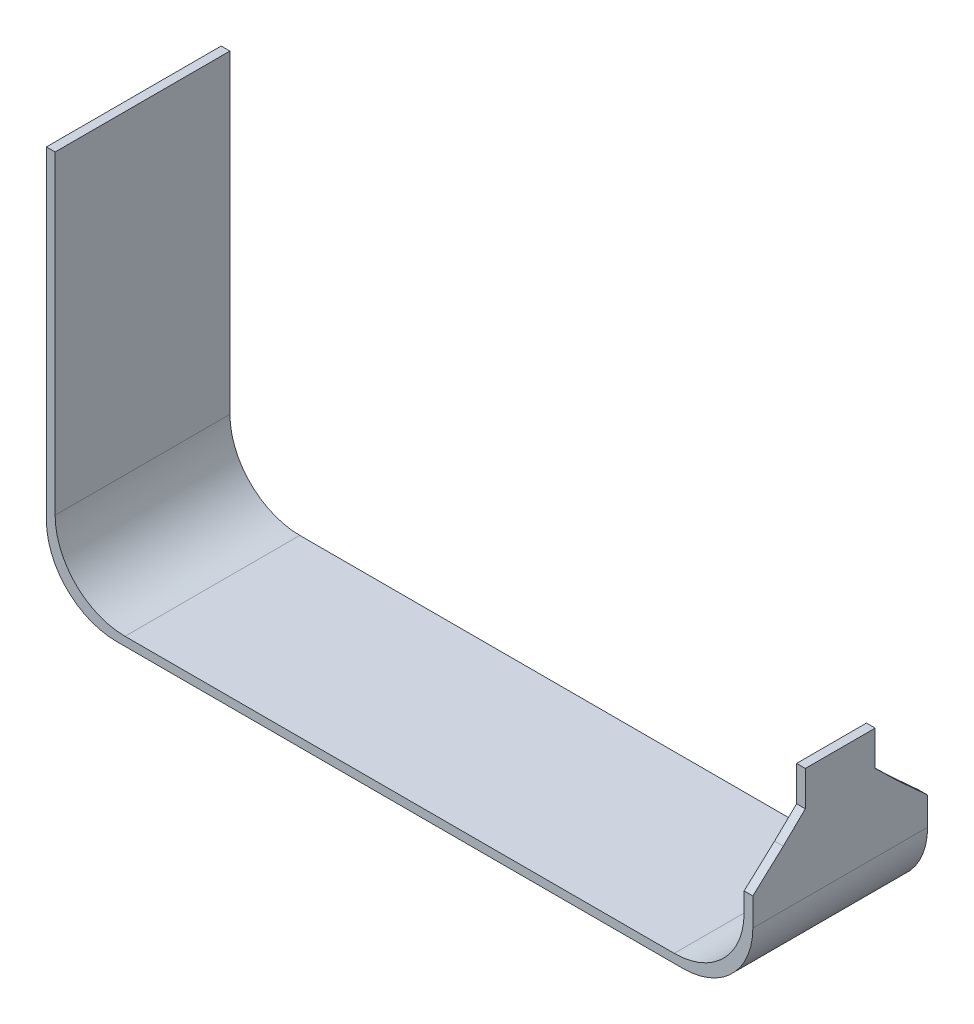
SolidWorks part; units mm, degrees
material "Copper"
ref_plane "Front Plane" through (0, 0, 0) normal (0, 0, 1) x (1, 0, 0)
ref_plane "Top Plane" through (0, 0, 0) normal (0, 1, 0) x (1, 0, 0)
ref_plane "Right Plane" through (0, 0, 0) normal (1, 0, 0) x (0, 0, -1)
sketch "Sketch1" plane through (0, 0, 0) normal (0, 1, 0) x (1, 0, 0)
  line L1 (-17.0372, 5.9349) -> (11.5628, 5.9349)
  line L2 (-17.0372, 5.9349) -> (-17.0372, 0.9349)
  line L3 (-17.0372, 0.9349) -> (11.5628, 0.9349)
  line L4 (11.5628, 5.9349) -> (11.5628, 0.9349)
  dimension "D1" = 28.6
  dimension "D2" = 5
extrude "Boss-Extrude1" add sketch "Sketch1" along normal blind 0.25
sketch "Sketch2" plane through (-17.0372, 0, 0) normal (-1, 0, 0) x (0, 0, 1)
  line L1 (-5.9349, 0.25) -> (-0.9349, 0.25)
  line L2 (-5.9349, 0.25) -> (-5.9349, 11.25)
  line L3 (-5.9349, 11.25) -> (-0.9349, 11.25)
  line L4 (-0.9349, 0.25) -> (-0.9349, 11.25)
  dimension "D1" = 11
extrude "Boss-Extrude2" add sketch "Sketch2" against normal blind 0.25
sketch "Sketch3" plane through (11.5628, 0, 0) normal (1, 0, 0) x (0, 0, -1)
  line L1 (0.9349, 0.25) -> (5.9363, 0.25)
  line L2 (0.9349, 0.25) -> (0.9349, 2.75)
  line L4 (5.9363, 0.25) -> (5.9363, 2.75)
  line L6 (3.4356, 5.2059) -> (2.4356, 5.2059)
  line L7 (3.4356, 5.2059) -> (4.4356, 5.2059)
  line L8 (2.4356, 5.2059) -> (2.4356, 4.2059)
  line L9 (4.4356, 5.2059) -> (4.4356, 4.2059)
  line L10 (2.4356, 4.2059) -> (0.9349, 2.75)
  line L11 (4.4356, 4.2059) -> (5.9363, 2.75)
  point P1 (3.4356, 2.75)
  point P2 (3.4356, 2.75)
  point P7 (3.4356, 5.25)
  dimension "D1" = 1
  dimension "D2" = 1
  dimension "D3" = 1
  dimension "D4" = 1
extrude "Boss-Extrude3" add sketch "Sketch3" against normal blind 0.25
fillet "Fillet3" radius 2 2 edges at (11.3128, 0.25, -3.4349) (-16.7872, 0.25, -3.4349)
fillet "Fillet4" radius 2 2 edges at (11.5628, 0, -3.4349) (-17.0372, 0, -3.4349)
sketch "Sketch4" plane through (0, 0, 0) normal (0, -1, 0) x (1, 0, 0)
  line L0 (-15.0372, -0.9349) -> (9.5628, -0.9349) construction
  line L1 (2.9233, -0.9349) -> (9.5628, -0.9349)
  line L2 (2.9233, -0.9349) -> (2.9233, -5.9349)
  line L3 (2.9233, -5.9349) -> (9.5628, -5.9349)
  line L4 (9.5628, -0.9349) -> (9.5628, -5.9349)
extrude "Cut-Extrude1" cut sketch "Sketch4" against normal blind 1.5
sketch "Sketch5" plane through (2.9233, 0, 0) normal (1, 0, 0) x (0, 0, -1)
  line L1 (0.9349, 0) -> (5.9349, 0)
  line L2 (0.9349, 0) -> (0.9349, 3.5954)
  line L3 (0.9349, 3.5954) -> (5.9349, 3.5954)
  line L4 (5.9349, 0) -> (5.9349, 3.5954)
  dimension "D1" = 5
extrude "Boss-Extrude4" add sketch "Sketch5" along normal blind 0.25
fillet "Fillet5" radius 2 1 edges at (2.9233, 0.25, -3.4349)
fillet "Fillet6" radius 2 1 edges at (3.1733, 0, -3.4349)
sketch "Sketch6" plane through (3.1733, 0, 0) normal (1, 0, 0) x (0, 0, -1)
  line L0 (0.9349, 2.75) -> (2.4356, 4.2059)
  line L1 (2.4356, 4.2059) -> (2.4356, 5.2059)
  line L2 (2.4356, 5.2059) -> (4.4356, 5.2059)
  line L3 (4.4356, 5.2059) -> (4.4356, 4.2059)
  line L4 (0.9349, 2.75) -> (5.9349, 2.75)
  line L6 (5.9349, 2) -> (5.9349, 3.5954) construction
  line L7 (5.9349, 2.75) -> (4.4356, 4.2059)
extrude "Boss-Extrude5" add sketch "Sketch6" against normal blind 0.25
sketch "Sketch7" plane through (3.1733, 0, 0) normal (1, 0, 0) x (0, 0, -1)
  line L0 (1.8062, 3.5954) -> (0.9349, 3.5954)
  line L1 (0.9349, 3.5954) -> (0.9349, 2.7977)
  line L2 (0.9349, 3.5954) -> (0.9349, 2) construction
  line L3 (0.9349, 2.7977) -> (1.8062, 3.5954)
  line L4 (5.0643, 3.5954) -> (5.9349, 3.5954)
  line L5 (5.9349, 3.5954) -> (5.9349, 2.7977)
  line L6 (5.9349, 2) -> (5.9349, 3.5954) construction
  line L7 (5.9349, 2.7977) -> (5.0643, 3.5954)
extrude "Cut-Extrude2" cut sketch "Sketch7" against normal blind 0.25
sketch "Sketch8" plane through (0, 0, -5.9363) normal (0, 0, -1) x (-1, 0, 0)
  line L1 (-14.6356, -2.0851) -> (-7.7597, -2.0851)
  line L2 (-14.6356, -2.0851) -> (-14.6356, 7.2509)
  line L3 (-14.6356, 7.2509) -> (-7.7597, 7.2509)
  line L4 (-7.7597, -2.0851) -> (-7.7597, 7.2509)
extrude "Cut-Extrude3" cut sketch "Sketch8" against normal blind 5.25
